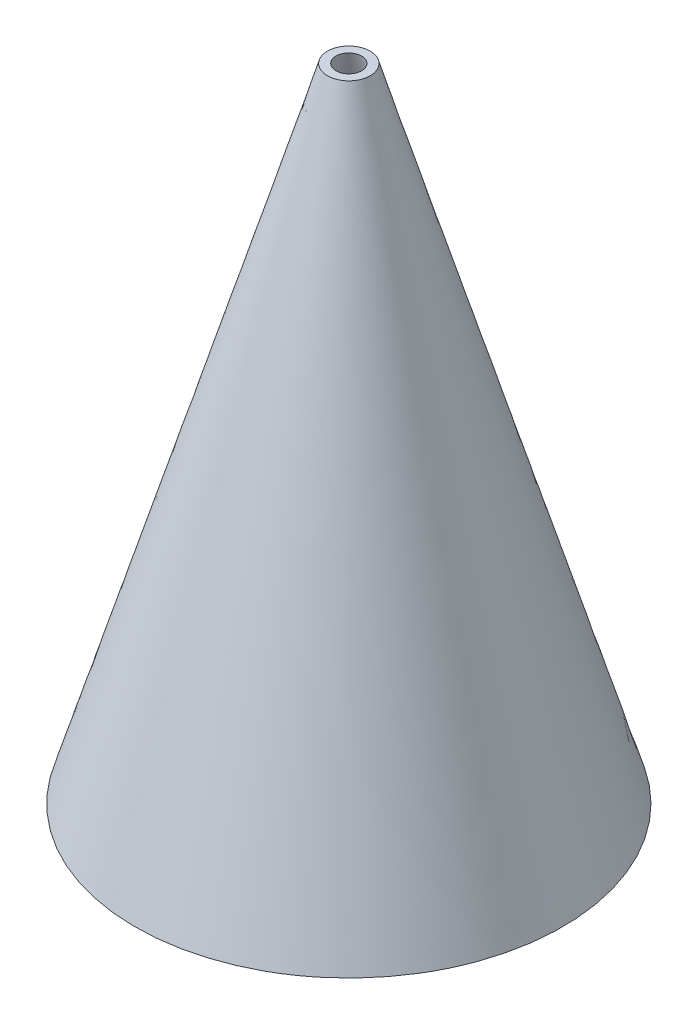
SolidWorks part; units mm, degrees
ref_plane "Front Plane" through (0, 0, 0) normal (0, 0, 1) x (1, 0, 0)
ref_plane "Top Plane" through (0, 0, 0) normal (0, 1, 0) x (1, 0, 0)
ref_plane "Right Plane" through (0, 0, 0) normal (1, 0, 0) x (0, 0, -1)
sketch "Sketch1" plane through (0, 0, 0) normal (0, 1, 0) x (1, 0, 0)
  circle A0 centre (0, 0) radius 50
  dimension "D1" = 100
ref_plane "Plane1" through (0, 150, 0) normal (0, 1, 0) x (1, 0, 0)
sketch "Sketch2" plane through (0, 150, 0) normal (0, 1, 0) x (1, 0, 0)
  circle A0 centre (0, 0) radius 5
  dimension "D1" = 10
loft "Loft1" add profiles "Sketch2", "Sketch1" connector at (-4.4392, 150, -2.3007) connector at (-38.0814, 0, -32.4007)
sketch "Sketch3" plane through (0, 150, 0) normal (0, 1, 0) x (1, 0, 0)
  circle A0 centre (0, 0) radius 3
  dimension "D1" = 6
sketch "Sketch4" plane through (0, 0, 0) normal (0, 1, 0) x (1, 0, 0)
  circle A0 centre (0, 0) radius 48
  dimension "D1" = 96
loft "Cut-Loft1" cut profiles "Sketch4", "Sketch3" connector at (44.2065, 0, -18.7026) connector at (1.4683, 150, -2.6161)
